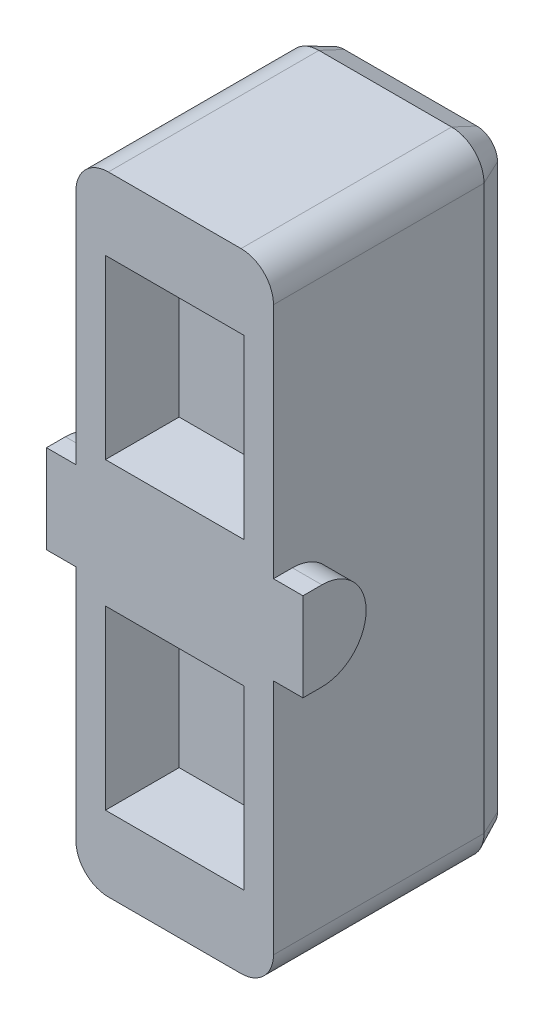
SolidWorks part; units mm, degrees
ref_plane "Plan de face" through (0, 0, 0) normal (0, 0, 1) x (1, 0, 0)
ref_plane "Plan de dessus" through (0, 0, 0) normal (0, 1, 0) x (1, 0, 0)
ref_plane "Plan de droite" through (0, 0, 0) normal (1, 0, 0) x (0, 0, -1)
sketch "Esquisse2" plane through (0, 0, 0) normal (0, 0, 1) x (1, 0, 0)
  line L1 (1.1, 0) -> (5.6, 0)
  line L2 (0, 1.1) -> (0, 20.2)
  line L3 (1.1, 21.3) -> (5.6, 21.3)
  line L4 (6.7, 1.1) -> (6.7, 20.2)
  arc A0 (5.6, 21.3) -> (6.7, 20.2) centre (5.6, 20.2) cw
  arc A1 (5.6, 0) -> (6.7, 1.1) centre (5.6, 1.1) ccw
  arc A2 (1.1, 0) -> (0, 1.1) centre (1.1, 1.1) cw
  arc A3 (0, 20.2) -> (1.1, 21.3) centre (1.1, 20.2) cw
  point P7 (6.7, 21.3)
  point P12 (0, 0)
  point P15 (0, 21.3)
  dimension "D3" = 1.1
  dimension "D1" = 6.7
  dimension "D2" = 21.3
extrude "Boss.-Extru.1" add sketch "Esquisse2" along normal blind 8
sketch "Esquisse3" plane through (0, 0, 8) normal (0, 0, 1) x (1, 0, 0)
  line L0 (0, 20.2) -> (0, 1.1) construction
  line L1 (1, 18.8) -> (5.7, 18.8)
  line L2 (1, 18.8) -> (1, 12.8)
  line L3 (1, 12.8) -> (5.7, 12.8)
  line L4 (5.7, 18.8) -> (5.7, 12.8)
  line L5 (6.7, 1.1) -> (6.7, 20.2) construction
  line L6 (5.6, 21.3) -> (1.1, 21.3) construction
  line L8 (1.1, 0) -> (5.6, 0) construction
  line L9 (1, 8.5) -> (5.7, 8.5)
  line L10 (1, 8.5) -> (1, 2.5)
  line L11 (1, 2.5) -> (5.7, 2.5)
  line L12 (5.7, 8.5) -> (5.7, 2.5)
  line L13 (-7.1761, 15.8) -> (15.2275, 15.8) construction
  dimension "D2" = 6
  dimension "D3" = 1
  dimension "D4" = 1
  dimension "D5" = 2.5
  dimension "D6" = 6
  dimension "D8" = 1
  dimension "D9" = 2.5
  dimension "D10" = 5.5
  dimension "D11" = 1
chamfer "Chanfrein1" distance 0.4 angle 65 8 edges at (3.35, 0, 0) (6.3778, 0.3222, 0) (0.3222, 0.3222, 0) (6.7, 10.65, 0) (0, 10.65, 0) (6.3778, 20.9778, 0) (0.3222, 20.9778, 0) (3.35, 21.3, 0) first distance on face at (3.35, 10.65, 0)
sketch "Esquisse5" plane through (0, 0, 0) normal (0, 0, 1) x (1, 0, 0)
  line L1 (1.54, 5.9) -> (5.1595, 5.9)
  line L2 (5.1595, 5.9) -> (3.3498, 1.9)
  line L3 (3.3498, 1.9) -> (1.54, 5.9)
  line L4 (3.3498, 3.3556) -> (2.47, 5.3)
  line L5 (2.47, 5.3) -> (4.2295, 5.3)
  line L6 (4.2295, 5.3) -> (3.3498, 3.3556)
  line L7 (5.6, 0.4) -> (1.1, 0.4) construction
  line L8 (1.54, 15.4) -> (5.16, 15.4)
  line L9 (5.16, 15.4) -> (3.35, 19.4)
  line L10 (3.35, 19.4) -> (1.54, 15.4)
  line L11 (2.4701, 16) -> (4.2299, 16)
  line L12 (4.2299, 16) -> (3.35, 17.9446)
  line L13 (3.35, 17.9446) -> (2.4701, 16)
  line L14 (1.1, 20.9) -> (5.6, 20.9) construction
  line L15 (0.4, 1.1) -> (0.4, 20.2) construction
  line L16 (6.3, 20.2) -> (6.3, 1.1) construction
  line L17 (6.3, 9.6541) -> (0.4, 9.6541) construction
  text T0 "<b>RNG</b>" font "Century Gothic" height 2.5
  dimension "D1" = 0.6
  dimension "D2" = 0.6
  dimension "D3" = 0.6
  dimension "D4" = 1.8098
  dimension "D5" = 1.8097
  dimension "D6" = 4
  dimension "D7" = 1.5
  dimension "D8" = 0.6
  dimension "D9" = 0.6
  dimension "D10" = 0.6
  dimension "D11" = 4
  dimension "D12" = 1.81
  dimension "D13" = 1.81
  dimension "D14" = 1.5
  dimension "D15" = 1.14
  dimension "D16" = 1.1405
  dimension "D17" = 1.14
extrude "Boss.-Extru.2" add sketch "Esquisse5<4>" against normal blind 0.2
sketch "Esquisse5<4>" plane through (0, 0, 0) normal (0, 0, 1) x (1, 0, 0) same geometry as "Esquisse5"
extrude "Enlèv. mat.-Extru.3" cut sketch "Esquisse5" along normal blind 0.2
extrude "Enlèv. mat.-Extru.4" cut sketch "Esquisse3" against normal blind 2.5
sketch "Esquisse6" plane through (0, 0, 0) normal (-1, 0, 0) x (0, 0, 1)
  line L0 (-8.8899, 10.65) -> (18.0179, 10.65) construction
  line L1 (8, 20.2) -> (0.8578, 20.2) construction
  line L2 (8, 1.1) -> (0.8578, 1.1) construction
  line L3 (0.8578, 20.2) -> (0.8578, 1.1) construction
  line L5 (7.3578, 12.15) -> (8, 12.15)
  line L6 (8, 1.1) -> (8, 20.2) construction
  line L7 (8, 12.15) -> (8, 9.15)
  line L8 (8, 9.15) -> (7.3578, 9.15)
  arc A0 (7.3578, 9.15) -> (7.3578, 12.15) centre (7.3578, 10.65) cw
  dimension "D4" = 1.5
  dimension "D1" = 9.55
  dimension "D2" = 9.55
  dimension "D3" = 0
  dimension "D5" = 6.5
extrude "Boss.-Extru.3" add sketch "Esquisse6" along normal blind 1 and the other way blind 7.7
